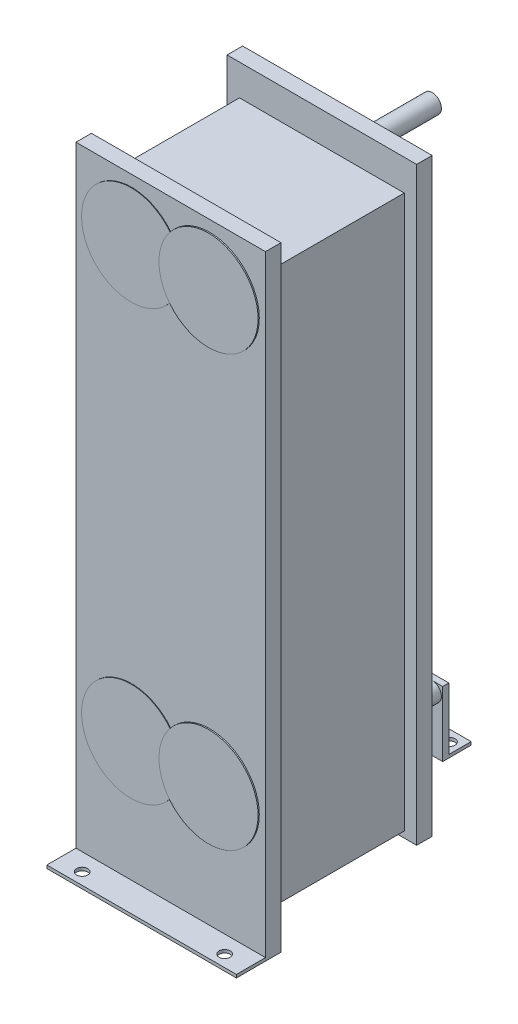
SolidWorks part; units mm, degrees
ref_plane "Front" through (0, 0, 0) normal (0, 0, 1) x (1, 0, 0)
ref_plane "Top" through (0, 0, 0) normal (0, 1, 0) x (1, 0, 0)
ref_plane "Right" through (0, 0, 0) normal (1, 0, 0) x (0, 0, -1)
sketch "Эскиз1" plane through (0, 0, 0) normal (0, 0, 1) x (1, 0, 0)
  line L1 (-153, 496) -> (153, 496)
  line L2 (-153, 496) -> (-153, -496)
  line L3 (-153, -496) -> (153, -496)
  line L4 (153, 496) -> (153, -496)
  line L5 (-153, 496) -> (153, -496) construction
  line L6 (-153, -496) -> (153, 496) construction
  point P0 (0, 0)
  dimension "D1" = 306
  dimension "D2" = 992
extrude "Вытянуть1" add sketch "Эскиз1" along normal blind 25
ref_plane "Плоскость1" through (0, 0, -219) normal (0, 0, -1) x (-1, 0, 0)
sketch "Эскиз3" plane through (0, 0, -219) normal (0, 0, -1) x (-1, 0, 0)
  line L0 (153, 496) -> (153, -496) construction
  line L1 (-153, 496) -> (153, 496)
  line L2 (-153, 496) -> (-153, -456)
  line L3 (-153, -456) -> (153, -456)
  line L4 (153, 496) -> (153, -456)
  line L5 (153, -496) -> (-153, -496) construction
  dimension "D1" = 40
extrude "Вытянуть2" add sketch "Эскиз3" along normal blind 25
sketch "Эскиз15" plane through (0, 0, 0) normal (0, 0, -1) x (-1, 0, 0)
  line L0 (-153, 496) -> (153, 496) construction
  line L1 (133, 446) -> (-133, 446)
  line L2 (133, 446) -> (133, -446)
  line L3 (133, -446) -> (-133, -446)
  line L4 (-133, 446) -> (-133, -446)
  line L5 (133, 446) -> (-133, -446) construction
  line L6 (133, -446) -> (-133, 446) construction
  line L7 (153, 496) -> (153, -496) construction
  point P0 (0, 0)
  dimension "D1" = 50
  dimension "D2" = 20
sketch "Эскиз17" plane through (0, 0, 25) normal (0, 0, 1) x (1, 0, 0)
  line L0 (0, 398) -> (0, 496) construction
  line L1 (-63, 398) -> (63, 398) construction
  line L5 (-63, 398) -> (-63, -296) construction
  line L6 (-63, -296) -> (63, -296) construction
  line L7 (63, 398) -> (63, -296) construction
  line L8 (153, 496) -> (-153, 496) construction
  line L9 (-153, -496) -> (153, -496) construction
  circle A0 centre (-63, -296) radius 28.5
  circle A1 centre (63, -296) radius 28.5
  circle A2 centre (-63, 398) radius 28.5
  circle A3 centre (63, 398) radius 28.5
  dimension "D1" = 57
  dimension "D4" = 200
  dimension "D2" = 126
  dimension "D3" = 694
extrude "Extrude3" add sketch "Эскиз15" along normal up to surface (219 mm away) up to face at (0, 20, -219)
sketch "Sketch3" plane through (0, -496, 0) normal (0, -1, 0) x (1, 0, 0)
  line L0 (0, 221.3158) -> (0, -443) construction
  line L1 (-153, 25) -> (153, 25)
  line L2 (-153, 25) -> (-153, 72)
  line L3 (-153, 72) -> (153, 72)
  line L4 (153, 25) -> (153, 72)
  line L5 (-17, -407) -> (17, -443) construction
  line L6 (-17, -443) -> (17, -443)
  line L7 (-17, -443) -> (-17, -407)
  line L8 (-17, -407) -> (17, -407)
  line L9 (17, -443) -> (17, -407)
  line L10 (-17, -443) -> (17, -407) construction
  line L11 (-115, 53) -> (0, 53) construction
  line L12 (0, 53) -> (115, 53) construction
  circle A0 centre (0, -425) radius 9
  circle A1 centre (-115, 53) radius 9
  circle A2 centre (115, 53) radius 9
  dimension "D4" = 230
  dimension "D5" = 18
  dimension "D8" = 18
  dimension "D9" = 18
  dimension "D1" = 47
  dimension "D2" = 34
  dimension "D3" = 36
  dimension "D6" = 19
  dimension "D7" = 478
extrude "Extrude6" add sketch "Sketch3" against normal blind 5
sketch "Sketch4" plane through (0, 0, -407) normal (0, 0, 1) x (1, 0, 0)
  line L1 (-17, -496) -> (17, -496)
  line L2 (-17, -496) -> (-17, -391)
  line L3 (-17, -391) -> (17, -391)
  line L4 (17, -496) -> (17, -391)
  dimension "D1" = 105
extrude "Extrude7" add sketch "Sketch4" along normal blind 10
sketch "Sketch5" plane through (0, 0, -244) normal (0, 0, -1) x (-1, 0, 0)
  line L0 (0, 550.099) -> (0, -710.8326) construction
  line L1 (153, 496) -> (-153, 496) construction
  line L2 (-153, -456) -> (153, -456) construction
  circle A0 centre (0, -406) radius 15
  circle A1 centre (0, 416) radius 15
  dimension "D1" = 80
  dimension "D2" = 50
  dimension "D3" = 30
extrude "Extrude8" add sketch "Sketch5" along normal up to surface (153 mm away) up to face at (0, -443.5, -397)
extrude "Бобышка-Вытянуть1" add sketch "Эскиз17" along normal blind 1
sketch "Эскиз18" plane through (0, 0, 26) normal (0, 0, 1) x (1, 0, 0)
  circle A0 centre (-63, 398) radius 80
  circle A1 centre (-63, -296) radius 80
  dimension "D1" = 160
  dimension "D2" = 160
extrude "Бобышка-Вытянуть2" add sketch "Эскиз18" against normal blind 20
sketch "Эскиз19" plane through (0, 0, 26) normal (0, 0, 1) x (1, 0, 0)
  circle A0 centre (63, 398) radius 28.5
  circle A1 centre (63, -296) radius 28.5
  dimension "D1" = 57
  dimension "D2" = 57
extrude "Бобышка-Вытянуть3" add sketch "Эскиз19" along normal blind 1
sketch "Эскиз20" plane through (0, 0, 27) normal (0, 0, 1) x (1, 0, 0)
  circle A0 centre (63, 398) radius 80
  circle A1 centre (63, -296) radius 80
  dimension "D1" = 160
  dimension "D2" = 160
extrude "Бобышка-Вытянуть4" add sketch "Эскиз20" against normal blind 20
ref_plane "Плоскость2" through (0, 0, 0) normal (1, 0, 0) x (0, 0, -1)
ref_axis "Ось1" through (63, 398, 25) along (0, 0, 1)
ref_axis "Ось2" through (-63, 398, 25) along (0, 0, 1)
ref_axis "Ось3" through (-63, -296, 25) along (0, 0, 1)
ref_axis "Ось4" through (63, -296, 25) along (0, 0, 1)
